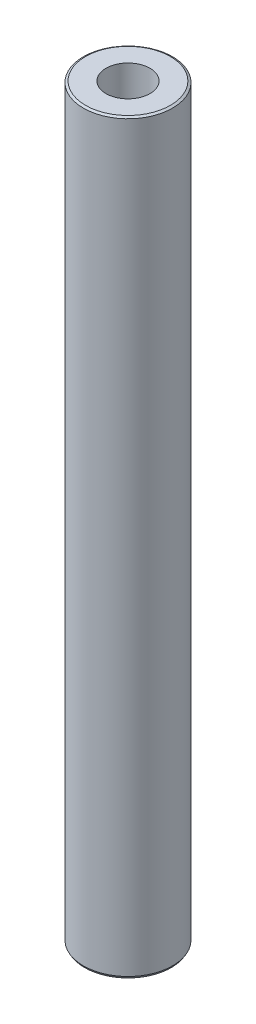
SolidWorks part; units mm, degrees
ref_plane "Front Plane" through (0, 0, 0) normal (0, 0, 1) x (1, 0, 0)
ref_plane "Top Plane" through (0, 0, 0) normal (0, 1, 0) x (1, 0, 0)
ref_plane "Right Plane" through (0, 0, 0) normal (1, 0, 0) x (0, 0, -1)
sketch "Sketch1" plane through (0, 0, 0) normal (0, 1, 0) x (1, 0, 0)
  circle A0 centre (0, 0) radius 30
  dimension "SHAFT_OD" = 60
extrude "Boss-Extrude1" add sketch "Sketch1" along normal blind 502.1792
sketch "Sketch2" plane through (0, 0, 0) normal (0, 1, 0) x (1, 0, 0)
  circle A0 centre (0, 0) radius 14.8071
  dimension "BORE_D" = 29.6141
extrude "Cut-Extrude1" cut sketch "Sketch2" along normal through all
chamfer "Chamfer1" distance 0.8576 angle 60 2 edges at (0, 502.1792, 30) (0, 0, 30) first distance on face at (0, 502.1792, 30) first distance on face at (0, 0, 14.8071)
